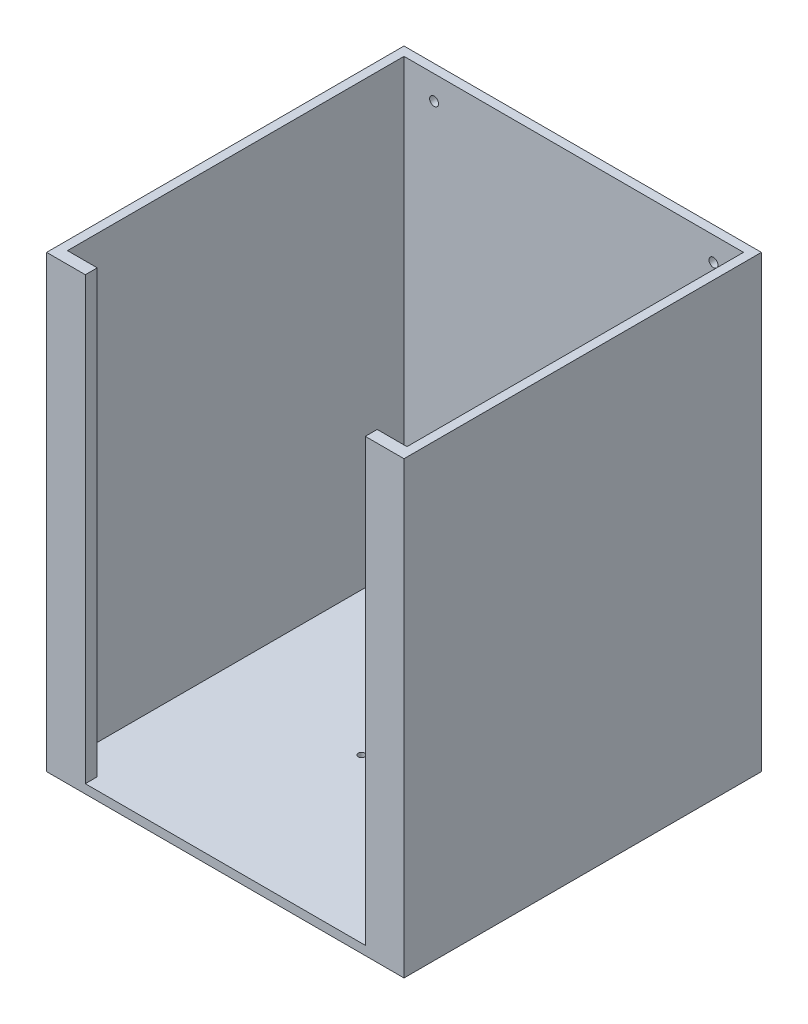
SolidWorks part; units mm, degrees
other "Markup1"
sketch "Sketch8" plane through (60, 0, -60) normal (0.7052, -0.7014, -0.1039) x (0.274, 0.4048, -0.8724)
other "Markup2"
sketch "Sketch9" plane through (60, 0, -60) normal (0.9922, -0.0018, -0.1244) x (-0.0942, 0.6423, -0.7606)
ref_plane "Front Plane" through (0, 0, 0) normal (0, 0, 1) x (1, 0, 0)
ref_plane "Top Plane" through (0, 0, 0) normal (0, 1, 0) x (1, 0, 0)
ref_plane "Right Plane" through (0, 0, 0) normal (1, 0, 0) x (0, 0, -1)
sketch "Sketch1" plane through (0, 0, 0) normal (0, 1, 0) x (1, 0, 0)
  line L5 (-60, 60) -> (60, 60)
  line L6 (-60, 60) -> (-60, -60)
  line L7 (-60, -60) -> (60, -60)
  line L8 (60, 60) -> (60, -60)
  dimension "D1" = 120
  dimension "D2" = 120
  dimension "D3" = 60
  dimension "D4" = 60
extrude "Main-Body" add sketch "Sketch1" along normal blind 151
sketch "Sketch11" plane through (0, 151, 0) normal (0, 1, 0) x (1, 0, 0)
  line L1 (57, -60) -> (-57, -60)
  line L5 (60, 60) -> (-60, 60) construction
  line L6 (-57, -60) -> (57, -60)
  line L14 (-57, -60) -> (-57, 57)
  line L15 (-57, 57) -> (57, 57)
  line L16 (57, -60) -> (57, 57)
  point P0 (0, -1)
  dimension "D1" = 58
  dimension "D2" = 3
  dimension "D3" = 117
  dimension "D4" = 57
  dimension "D5" = 57
extrude "Hollow" cut sketch "Sketch11" against normal blind 148 contours L14 L6 L16 L15
sketch "Sketch12" plane through (57, 0, 0) normal (-1, 0, 0) x (0, 0, 1)
  line L1 (56, 151) -> (60, 151)
  line L2 (56, 151) -> (56, 3)
  line L3 (56, 3) -> (60, 3)
  line L4 (60, 151) -> (60, 3)
  point P4 (0, 0)
  dimension "D1" = 4
extrude "Boss-Extrude1" add sketch "Sketch12" along normal blind 10
sketch "Sketch13" plane through (-57, 0, 0) normal (1, 0, 0) x (0, 0, -1)
  line L1 (-60, 151) -> (-56, 151)
  line L2 (-60, 151) -> (-60, 3)
  line L3 (-60, 3) -> (-56, 3)
  line L4 (-56, 151) -> (-56, 3)
  point P4 (0, 0)
  point P6 (0, 0)
  dimension "D1" = 4
extrude "Boss-Extrude2" add sketch "Sketch13" along normal blind 10
sketch "Sketch14" plane through (0, 0, 0) normal (0, -1, 0) x (0, 0, 1)
  line L0 (-60, -60) -> (-60, 60) construction
  circle A0 centre (-2.225, 9) radius 1.1
  circle A1 centre (5.275, 9) radius 1.1
  circle A2 centre (5.275, -9) radius 1.1
  circle A3 centre (-2.225, -9) radius 1.1
  point P7 (-60, 0)
  dimension "D1" = 2.2
  dimension "D2" = 57.775
  dimension "D3" = 9
  dimension "D4" = 2
  dimension "D5" = 2
extrude "LED-Mounting-Holes" cut sketch "Sketch14" against normal up to next
sketch "Sketch15" plane through (0, 3, 0) normal (0, 1, 0) x (1, 0, 0)
  circle A0 centre (0, -0.05) radius 1.5
  circle A1 centre (-9, 2.225) radius 1.1 construction
  point P2 (0, 0)
  point P7 (-22.8623, 4.1124)
  dimension "D1" = 9
  dimension "D3" = 3
  dimension "D2" = 2.275
extrude "LED-Position" cut sketch "Sketch15" against normal blind 1
sketch "Sketch16" plane through (0, 0, -60) normal (0, 0, -1) x (-1, 0, 0)
  circle A0 centre (-46.9, 143) radius 1.5
  dimension "D1" = 13.1
  dimension "D2" = 8
extrude "Bolt-Hole-1" cut sketch "Sketch16" against normal up to next
pattern_linear "LPattern1" count 2 spacing 93.8 along (1, 0, 0) of "Bolt-Hole-1"
sketch "Sketch18" plane through (0, 0, 56) normal (0, 0, -1) x (-1, 0, 0)
  line L1 (55.2, 136) -> (53.6, 138.7713)
  line L2 (53.6, 138.7713) -> (50.4, 138.7713)
  line L3 (50.4, 138.7713) -> (48.8, 136)
  line L4 (48.8, 136) -> (50.4, 133.2287)
  line L5 (50.4, 133.2287) -> (53.6, 133.2287)
  line L6 (53.6, 133.2287) -> (55.2, 136)
  circle A0 centre (52, 136) radius 3.2 construction
  point P1 (0, 0)
  dimension "D1" = 15
  dimension "D2" = 5
extrude "Cut-Extrude5" cut sketch "Sketch18" against normal blind 2
